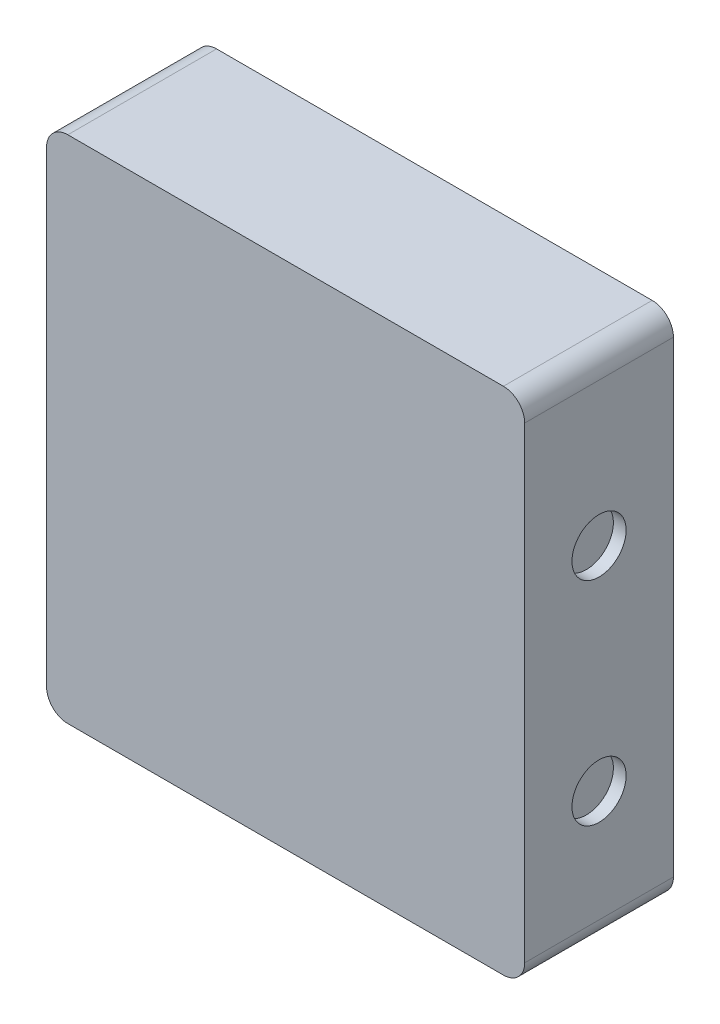
SolidWorks part; units mm, degrees
ref_plane "Front Plane" through (0, 0, 0) normal (0, 0, 1) x (1, 0, 0)
ref_plane "Top Plane" through (0, 0, 0) normal (0, 1, 0) x (1, 0, 0)
ref_plane "Right Plane" through (0, 0, 0) normal (1, 0, 0) x (0, 0, -1)
ref_plane "Plane1" through (0, 0, 31) normal (0, 0, 1) x (1, 0, 0)
sketch "Sketch1" plane through (0, 0, 31) normal (0, 0, 1) x (1, 0, 0)
  line L0 (-22.5, -20.5) -> (-22.5, -11) construction
  line L1 (-22.5, -11) -> (-22.5, 11) construction
  line L2 (-22.5, 11) -> (-22.5, 23.5) construction
  line L3 (-20.5, 25.5) -> (-4.9093, 25.5) construction
  line L4 (-4.9093, 25.5) -> (4.9093, 25.5) construction
  line L5 (4.9093, 25.5) -> (20.5, 25.5) construction
  line L6 (22.5, 23.5) -> (22.5, 11) construction
  line L7 (22.5, 11) -> (22.5, -11) construction
  line L8 (22.5, -11) -> (22.5, -20.5) construction
  line L9 (20.5, -22.5) -> (11, -22.5) construction
  line L10 (11, -22.5) -> (-11, -22.5) construction
  line L11 (-11, -22.5) -> (-20.5, -22.5) construction
  line L12 (-22.5, -20.5) -> (-22.5, -11)
  line L13 (-22.5, -11) -> (-22.5, 11)
  line L14 (-22.5, 11) -> (-22.5, 23.5)
  line L15 (-20.5, 25.5) -> (-4.9093, 25.5)
  line L16 (-4.9093, 25.5) -> (4.9093, 25.5)
  line L17 (4.9093, 25.5) -> (20.5, 25.5)
  line L18 (22.5, 23.5) -> (22.5, 11)
  line L19 (22.5, 11) -> (22.5, -11)
  line L20 (22.5, -11) -> (22.5, -20.5)
  line L21 (20.5, -22.5) -> (11, -22.5)
  line L22 (11, -22.5) -> (-11, -22.5)
  line L23 (-11, -22.5) -> (-20.5, -22.5)
  line L24 (-19.5, -18.5) -> (-19.5, -11)
  line L25 (-19.5, -11) -> (-19.5, 11)
  line L26 (-19.5, 11) -> (-19.5, 21.5)
  line L27 (-18.5, 22.5) -> (-4.9093, 22.5)
  line L28 (-4.9093, 22.5) -> (4.9093, 22.5)
  line L29 (4.9093, 22.5) -> (18.5, 22.5)
  line L30 (19.5, 21.5) -> (19.5, 11)
  line L31 (19.5, 11) -> (19.5, -11)
  line L32 (19.5, -11) -> (19.5, -18.5)
  line L33 (18.5, -19.5) -> (11, -19.5)
  line L34 (11, -19.5) -> (-11, -19.5)
  line L35 (-11, -19.5) -> (-18.5, -19.5)
  line L36 (-19.5, -19.5) -> (-19.5, -11) construction
  line L37 (-11, -19.5) -> (-19.5, -19.5) construction
  line L38 (19.5, -19.5) -> (11, -19.5) construction
  line L39 (19.5, -11) -> (19.5, -19.5) construction
  line L40 (19.5, 22.5) -> (19.5, 11) construction
  line L41 (4.9093, 22.5) -> (19.5, 22.5) construction
  line L42 (-19.5, 22.5) -> (-4.9093, 22.5) construction
  line L43 (-19.5, 11) -> (-19.5, 22.5) construction
  line L44 (-19.5, -18.5) -> (-19.5, -22.5)
  line L45 (19.5, -18.5) -> (19.5, -22.5)
  arc A0 (-20.5, 25.5) -> (-22.5, 23.5) centre (-20.5, 23.5) ccw construction
  arc A1 (22.5, 23.5) -> (20.5, 25.5) centre (20.5, 23.5) ccw construction
  arc A2 (20.5, -22.5) -> (22.5, -20.5) centre (20.5, -20.5) ccw construction
  arc A3 (-22.5, -20.5) -> (-20.5, -22.5) centre (-20.5, -20.5) ccw construction
  arc A4 (-20.5, 25.5) -> (-22.5, 23.5) centre (-20.5, 23.5) ccw
  arc A5 (22.5, 23.5) -> (20.5, 25.5) centre (20.5, 23.5) ccw
  arc A6 (20.5, -22.5) -> (22.5, -20.5) centre (20.5, -20.5) ccw
  arc A7 (-22.5, -20.5) -> (-20.5, -22.5) centre (-20.5, -20.5) ccw
  arc A12 (-19.5, -18.5) -> (-18.5, -19.5) centre (-18.5, -18.5) ccw
  arc A13 (-19.5, -19.5) -> (-19.5, -19.5) centre (-19.5, -19.5) ccw construction
  arc A14 (18.5, -19.5) -> (19.5, -18.5) centre (18.5, -18.5) ccw
  arc A15 (19.5, -19.5) -> (19.5, -19.5) centre (19.5, -19.5) ccw construction
  arc A16 (19.5, 21.5) -> (18.5, 22.5) centre (18.5, 21.5) ccw
  arc A17 (19.5, 22.5) -> (19.5, 22.5) centre (19.5, 22.5) ccw construction
  arc A18 (-18.5, 22.5) -> (-19.5, 21.5) centre (-18.5, 21.5) ccw
  arc A19 (-19.5, 22.5) -> (-19.5, 22.5) centre (-19.5, 22.5) ccw construction
  dimension "D2" = 1
  dimension "D1" = 3
extrude "Boss-Extrude4" add sketch "Sketch1" along normal blind 3 contours L12 A7 L23 L22 L21 A6 L20 L19 L18 A5 L17 L16 L15 A4 L14 L13 A18 L27 L28 L29 A16 L30 L31 L32 A14 L33 L34 L35 A12 L24 L25 L26 | L27 A18 L26 L25 L24 A12 L35 L34 L33 A14 L32 L31 L30 A16 L29 L28 | A14 L33 L34 L35 A12 L23 L22 L21 region at (-21.842, -15.75, 31) region at (0, -20.9937, 31) region at (0, 1.5, 31)
extrude "Boss-Extrude5" add sketch "Sketch1<3>" along normal up to surface (14 mm away) contours L12 A7 L23 L22 L21 A6 L20 L19 L18 A5 L17 L16 L15 A4 L14 L13 A18 L27 L28 L29 A16 L30 L31 L32 A14 L33 L34 L35 A12 L24 L25 L26 region at (-21.842, -15.75, 31)
sketch "Sketch1<3>" plane through (0, 0, 31) normal (0, 0, 1) x (1, 0, 0) same geometry as "Sketch1"
extrude "Boss-Extrude6" add sketch "Sketch1<4>" against normal blind 3 from surface contours L12 A7 L23 L22 L21 A6 L20 L19 L18 A5 L17 L16 L15 A4 L14 L13 A18 L27 L28 L29 A16 L30 L31 L32 A14 L33 L34 L35 A12 L24 L25 L26 | L27 A18 L26 L25 L24 A12 L35 L34 L33 A14 L32 L31 L30 A16 L29 L28 | A14 L33 L34 L35 A12 L23 L22 L21 region at (-21.842, -15.75, 31) region at (0, -20.9937, 31) region at (0, 1.5, 31) starting at face at (0, 3.9582, 45)
sketch "Sketch1<4>" plane through (0, 0, 31) normal (0, 0, 1) x (1, 0, 0) same geometry as "Sketch1"
sketch "Sketch2" plane through (0, -22.5, 0) normal (0, -1, 0) x (1, 0, 0)
  line L0 (-5, 38) -> (-5, 30.5)
  line L2 (-11, 30.5) -> (11, 30.5) construction
  line L4 (-5, 30.5) -> (5, 30.5)
  line L5 (5, 30.5) -> (5, 38)
  line L6 (5, 45) -> (-5, 45)
  line L7 (5, 38) -> (5, 45)
  line L8 (-5, 38) -> (5, 38)
  line L9 (-5, 45) -> (-5, 38)
  line L10 (5, 45) -> (-5, 45) construction
  line L11 (5, 38) -> (5, 45) construction
  line L12 (-5, 38) -> (5, 38)
  line L13 (-5, 45) -> (-5, 38) construction
  line M10 (19.5, 34) -> (-19.5, 34)
  line M13 (-20.5, 31) -> (20.5, 31)
  dimension "D1" = 0
extrude "Cut-Extrude1" cut sketch "Sketch2" against normal blind 3 contours L5 L0 M13 M10 | L12 L0 L5 M10 region at (0, -22.5, 36) region at (0, -22.5, 32.5)
sketch "Sketch3" plane through (0, 0, 0) normal (1, 0, 0) x (0, 0, -1)
  circle A0 centre (-38, -10) radius 2.55 construction
  circle A1 centre (-38, 10) radius 2.55 construction
  circle A2 centre (-38, -10) radius 2.55
  circle A3 centre (-38, 10) radius 2.55
extrude "Cut-Extrude2" cut sketch "Sketch3" against normal blind 1.2 from surface contours A3 | A2 region at (0, -10, 38) region at (0, 10, 38) starting at face at (22.5, 1.5, 38)
extrude "Cut-Extrude3" cut sketch "Sketch3<3>" along normal blind 1.2 from surface contours A2 | A3 region at (0, -10, 38) region at (0, 10, 38) starting at face at (-22.5, 1.5, 38)
sketch "Sketch3<3>" plane through (0, 0, 0) normal (1, 0, 0) x (0, 0, -1) same geometry as "Sketch3"
fillet "Fillet1" radius 0.7 23 edges at (12.25, -22.5, 34) (5, -21, 34) (-12.25, -22.5, 34) (19.5, -22.5, 38) (-5, -21, 31) (5, -21, 31) (0, -19.5, 34) (-19.5, -22.5, 38) (19.5, -0.5, 34) (19.2071, 22.2071, 34) (0, 22.5, 34) (-19.2071, 22.2071, 34) (19.5, -0.5, 42) (19.2071, 22.2071, 42) (0, 22.5, 42) (-19.2071, 22.2071, 42) (0, -19.5, 31) (-5, -21, 34) (0, -22.5, 42) (-19.5, -0.5, 34) (-19.5, -0.5, 42) (5, -19.5, 32.5) (-5, -19.5, 32.5)
